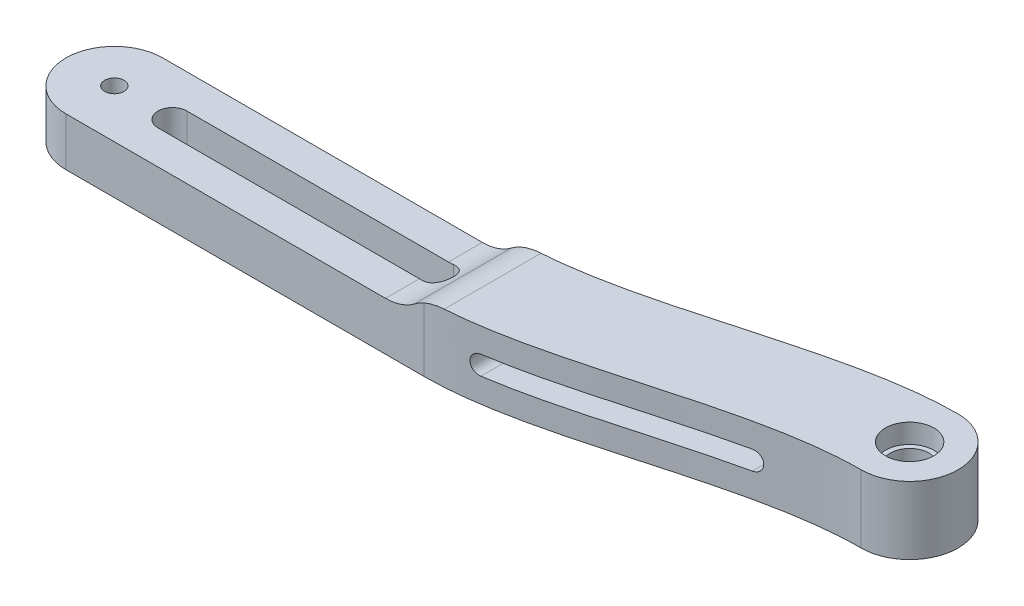
SolidWorks part; units mm, degrees
other "Markup1"
sketch "Sketch9" plane through (-108.3629, 11.4607, 16.5516) normal (-0.0199, 0.9913, 0.1302) x (0.9976, 0.0284, -0.0635)
ref_plane "Front Plane" through (0, 0, 0) normal (0, 0, 1) x (1, 0, 0)
ref_plane "Top Plane" through (0, 0, 0) normal (0, 1, 0) x (1, 0, 0)
ref_plane "Right Plane" through (0, 0, 0) normal (1, 0, 0) x (0, 0, -1)
sketch "Sketch1" plane through (0, 0, 0) normal (0, 1, 0) x (1, 0, 0)
  line L1 (-41.2996, 0) -> (-4.2996, 0)
  line L3 (-41.2996, -10) -> (-4.2996, -10)
  line L5 (-41.2996, 0) -> (0, 0) construction
  line L6 (52.3004, 0) -> (24.4927, 0) construction
  line L10 (43.2662, 7.2269) -> (23.9345, 7.2269) construction
  line L11 (52.3004, -10) -> (24.4927, -10) construction
  line L12 (43.2662, -2.7731) -> (23.9345, -2.7731) construction
  arc A0 (33.6004, -2.7731) -> (33.6004, 7.2269) centre (33.6004, 2.2269) ccw
  arc A1 (-41.2996, 0) -> (-41.2996, -10) centre (-41.2996, -5) ccw
  spline S0 degree 3 poles (-4.2996, 0) (7.2869, 0) (21.518, 7.2269) (33.6004, 7.2269) knots 0 0 0 0 1 1 1 1
  spline S1 degree 3 poles (-4.2996, -10) (7.2869, -10) (21.518, -2.7731) (33.6004, -2.7731) knots 0 0 0 0 1 1 1 1
  point P0 (0, 0)
  dimension "D2" = 5
  dimension "D4" = 5
  dimension "D1" = 10
  dimension "D3" = 10
  dimension "D5" = 37
  dimension "D6" = 37
  dimension "D7" = 74.9
  dimension "D8" = 10
extrude "Boss-Extrude1" add sketch "Sketch1" along normal blind 7
sketch "Sketch7" plane through (0, 0, 0) normal (0, -1, 0) x (1, 0, 0)
  line L0 (-41.2996, 10) -> (-4.2996, 10) construction
  line L1 (-1.2996, 10) -> (-41.2996, 10)
  line L2 (-1.2996, 10) -> (-1.2996, 0)
  line L3 (-1.2996, 0) -> (-41.2996, 0)
  arc A0 (-41.2996, 10) -> (-41.2996, 0) centre (-41.2996, 5) ccw
  point P4 (-20.6498, 5)
  dimension "D1" = 5
  dimension "D2" = 40
extrude "Boss-Extrude3" [suppressed] add sketch "Sketch7" along normal blind 2.5
sketch "Sketch3" plane through (0, 7, 0) normal (0, 1, 0) x (1, 0, 0)
  line L0 (-41.2996, -10) -> (-4.2996, -10) construction
  circle A0 centre (-41.2996, -5) radius 1
  arc A4 (-41.2996, 0) -> (-41.2996, -10) centre (-41.2996, -5) ccw construction
  point P11 (-46.2996, -5)
  dimension "D1" = 2
  dimension "D4" = 5
  dimension "D2" = 5
extrude "Cut-Extrude1" cut sketch "Sketch3" against normal blind 10.5
sketch "Sketch4" plane through (0, 7, 0) normal (0, 1, 0) x (1, 0, 0)
  line L0 (-41.2996, -10) -> (-4.2996, -10) construction
  line L1 (-46.2996, 0) -> (-4.2996, 0)
  line L2 (-46.2996, 0) -> (-46.2996, -10)
  line L3 (-46.2996, -10) -> (-4.2996, -10)
  line L4 (-4.2996, 0) -> (-4.2996, -10)
  line L5 (-46.2996, 0) -> (-4.2996, -10) construction
  line L6 (-46.2996, -10) -> (-4.2996, 0) construction
  circle A0 centre (-41.2996, -5) radius 1 construction
  point P4 (-25.2996, -5)
  dimension "D3" = 37
  dimension "D1" = 10
  dimension "D2" = 5
extrude "Cut-Extrude2" cut sketch "Sketch4" against normal blind 2
sketch "Sketch5" plane through (0, 0, 0) normal (0, -1, 0) x (1, 0, 0)
  circle A0 centre (33.6004, -2.2269) radius 1
  dimension "D1" = 2
fillet "Fillet2" [suppressed] radius 90
scale "Scale1" scale about centroid uniform scaling yes scale factor 2
sketch "Sketch10" plane through (0, -3.0905, 0) normal (0, -1, 0) x (1, 0, 0)
  circle A0 centre (67.4769, -7.1047) radius 5
  dimension "D1" = 10
extrude "Cut-Extrude5" cut sketch "Sketch10" against normal blind 4
fillet "Fillet3" radius 10 1 edges
fillet "Fillet4" radius 10 1 edges at (-8.3231, 10.9095, 7.3491)
sketch "Sketch12" plane through (0, 6.9095, 0) normal (0, 1, 0) x (1, 0, 0)
  line L0 (-70.3231, -7.3491) -> (-15.3231, -7.3491) construction
  line L1 (-70.3231, -4.3491) -> (-15.3231, -4.3491)
  line L2 (-70.3231, -10.3491) -> (-15.3231, -10.3491)
  arc A0 (-70.3231, -4.3491) -> (-70.3231, -10.3491) centre (-70.3231, -7.3491) ccw
  arc A1 (-15.3231, -10.3491) -> (-15.3231, -4.3491) centre (-15.3231, -7.3491) ccw
  arc A2 (-82.3231, 2.6509) -> (-82.3231, -17.3491) centre (-82.3231, -7.3491) ccw construction
  point P3 (-42.8231, -7.3491)
  dimension "D1" = 6
  dimension "D2" = 55
  dimension "D3" = 12
extrude "Cut-Extrude6" cut sketch "Sketch12" against normal through all both and the other way through all
sketch "Sketch14" plane through (0, 0, -2.6509) normal (0, 0, -1) x (-1, 0, 0)
  line L0 (-47.4769, 3.9095) -> (-2.4769, 3.9095) construction
  line L1 (-47.4769, 5.8734) -> (-2.4769, 5.8734)
  line L2 (-47.4769, 1.9457) -> (-2.4769, 1.9457)
  line L4 (-67.4769, -3.0905) -> (8.3231, -3.0905) construction
  line L6 (-77.4769, 10.9095) -> (-77.4769, -3.0905) construction
  arc A0 (-47.4769, 5.8734) -> (-47.4769, 1.9457) centre (-47.4769, 3.9095) ccw
  arc A1 (-2.4769, 1.9457) -> (-2.4769, 5.8734) centre (-2.4769, 3.9095) ccw
  point P2 (-24.9769, 3.9095)
  dimension "D1" = 45
  dimension "D2" = 30
  dimension "D3" = 7
extrude "Cut-Extrude7" cut sketch "Sketch14" against normal through all both and the other way through all
sketch "Sketch17" plane through (0, 10.9095, 0) normal (0, 1, 0) x (1, 0, 0)
  circle A0 centre (67.4769, 7.1047) radius 4
  dimension "D1" = 8
extrude "Cut-Extrude10" cut sketch "Sketch17" against normal through all
sketch "Sketch18" plane through (0, 10.9095, 0) normal (0, 1, 0) x (1, 0, 0)
  circle A0 centre (67.4769, 7.1047) radius 5
  dimension "D1" = 10
extrude "Cut-Extrude11" cut sketch "Sketch18" against normal blind 4
